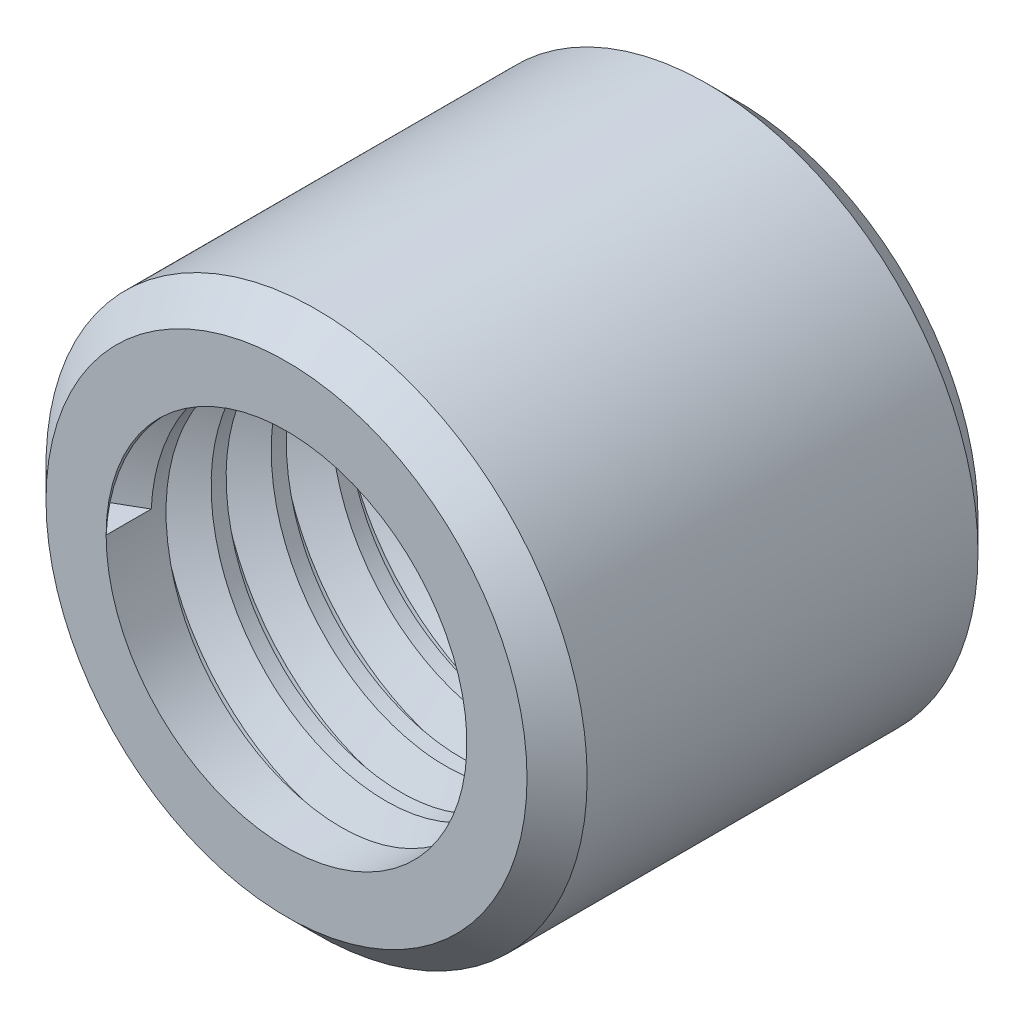
SolidWorks part; units mm, degrees
ref_plane "Plan de face" through (0, 0, 0) normal (0, 0, 1) x (1, 0, 0)
ref_plane "Plan de dessus" through (0, 0, 0) normal (0, 1, 0) x (1, 0, 0)
ref_plane "Plan de droite" through (0, 0, 0) normal (1, 0, 0) x (0, 0, -1)
sketch "Esquisse1" plane through (0, 0, 0) normal (0, 0, 1) x (1, 0, 0)
  circle A0 centre (0, 0) radius 9
  circle A1 centre (0, 0) radius 6
extrude "Boss.-Extru.1" add sketch "Esquisse1" along normal blind 15
thread "Filetage1" pitch 2 method cut profile "Profil de filetage1" start angle 0, offset 0, length 15, pitch 2, diameter 12
ref_plane "Plan1" through (-6, 0, 15) normal (0, -1, 0) x (-1, 0, 0)
sketch "Profil de filetage1" plane through (-6, 0, 15) normal (0, -1, 0) x (-1, 0, 0)
  line L0 (0, 0) -> (0, 2) construction
  line L1 (0, 0) -> (1.0825, 0.625)
  line L2 (1.0825, 0.625) -> (1.0825, 0.875)
  line L3 (1.0825, 0.875) -> (0, 1.5)
  line L4 (1.0825, 0.75) -> (0, 0.75) construction
  line L11 (0, 0) -> (0, 1.5)
  point P2 (0, 0)
  dimension "Pitch" = 2
  dimension "Profile_Angle" = 60
  dimension "Profile_Land" = 0.25
  dimension "Profile_Height" = 1.0825
chamfer "Chanfrein1" distance 1 angle 45 2 edges at (9, 0, 0) (9, 0, 15)
